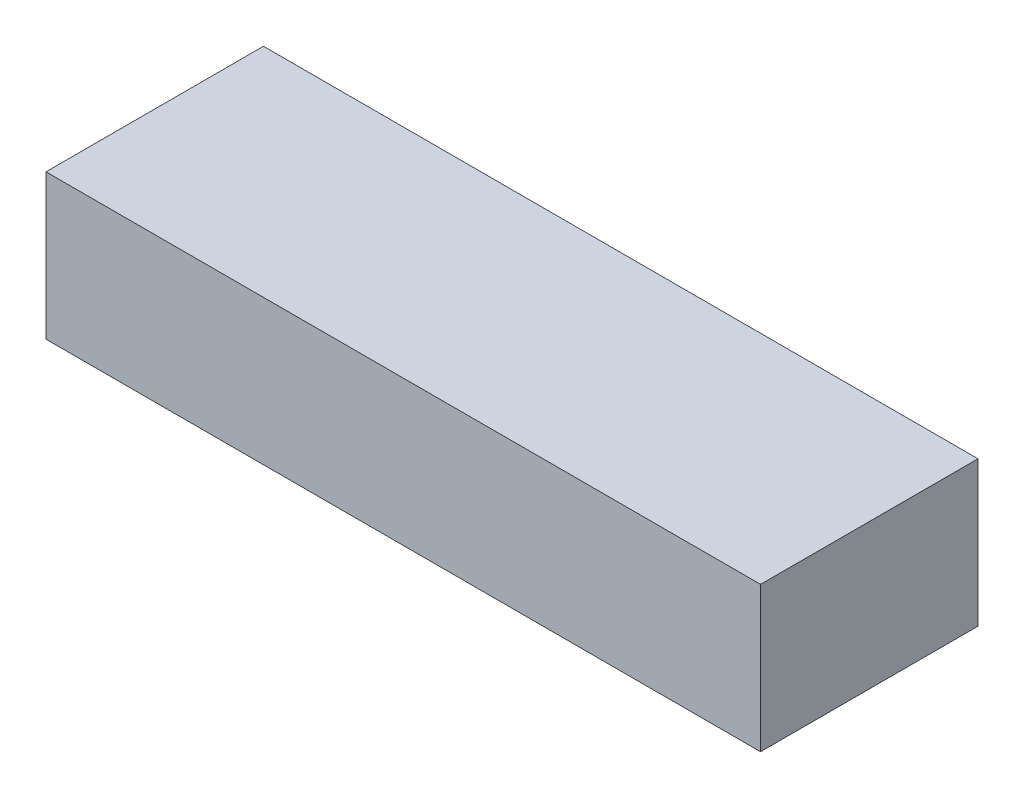
SolidWorks part; units mm, degrees
ref_plane "Front Plane" through (0, 0, 0) normal (0, 0, 1) x (1, 0, 0)
ref_plane "Top Plane" through (0, 0, 0) normal (0, 1, 0) x (1, 0, 0)
ref_plane "Right Plane" through (0, 0, 0) normal (1, 0, 0) x (0, 0, -1)
sketch "Sketch1" plane through (0, 0, 0) normal (0, 1, 0) x (1, 0, 0)
  line L1 (-69, -21) -> (69, -21)
  line L2 (-69, -21) -> (-69, 21)
  line L3 (-69, 21) -> (69, 21)
  line L4 (69, -21) -> (69, 21)
  line L5 (-69, -21) -> (69, 21) construction
  line L6 (-69, 21) -> (69, -21) construction
  point P0 (0, 0)
extrude "Boss-Extrude1" add sketch "Sketch1" along normal blind 28
